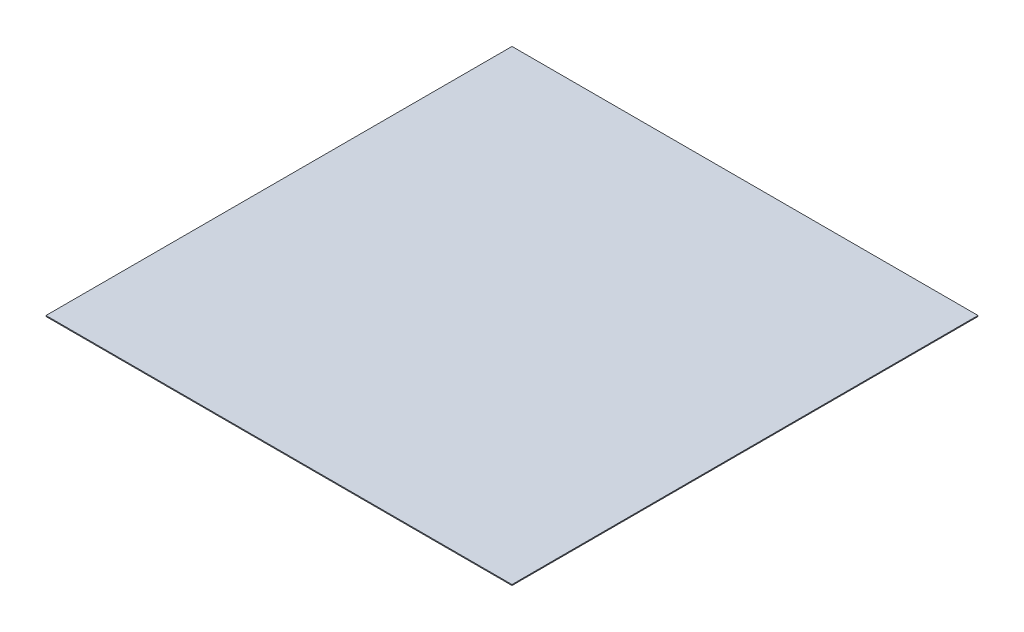
SolidWorks part; units mm, degrees
material "红木"
ref_plane "前视基准面" through (0, 0, 0) normal (0, 0, 1) x (1, 0, 0)
ref_plane "上视基准面" through (0, 0, 0) normal (0, 1, 0) x (1, 0, 0)
ref_plane "右视基准面" through (0, 0, 0) normal (1, 0, 0) x (0, 0, -1)
sketch "草图1" plane through (0, 0, 0) normal (0, 1, 0) x (1, 0, 0)
  line L1 (-500, -500) -> (500, -500)
  line L2 (-500, -500) -> (-500, 500)
  line L3 (-500, 500) -> (500, 500)
  line L4 (500, -500) -> (500, 500)
  line L5 (-500, -500) -> (500, 500) construction
  line L6 (-500, 500) -> (500, -500) construction
  point P0 (0, 0)
  dimension "D1" = 1000
extrude "凸台-拉伸1" add sketch "草图1" along normal blind 2
ref_axis "基准轴1" through (0, 2, 500) along (0, 0, -1)
